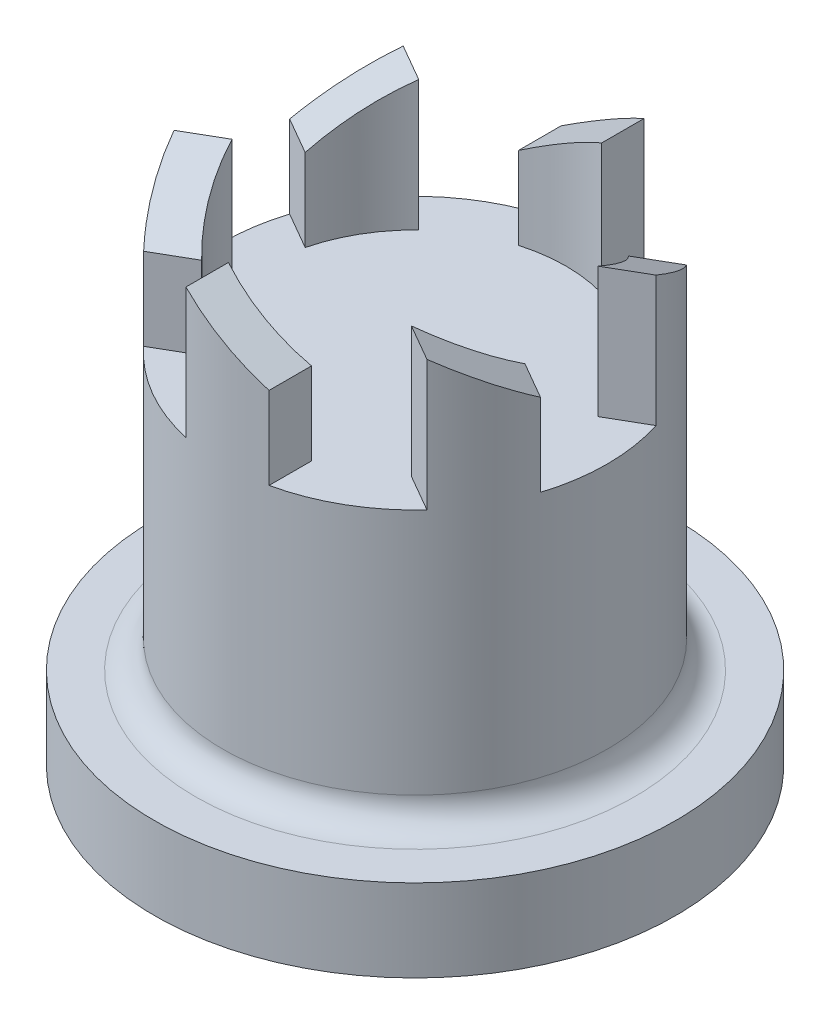
SolidWorks part; units mm, degrees
ref_plane "Front Plane" through (0, 0, 0) normal (0, 0, 1) x (1, 0, 0)
ref_plane "Top Plane" through (0, 0, 0) normal (0, 1, 0) x (1, 0, 0)
ref_plane "Right Plane" through (0, 0, 0) normal (1, 0, 0) x (0, 0, -1)
sketch "Sketch1" plane through (0, 0, 0) normal (0, 1, 0) x (1, 0, 0)
  circle A0 centre (0, 0) radius 7
  dimension "D1" = 14
extrude "Boss-Extrude1" add sketch "Sketch1" along normal blind 10
sketch "Sketch5" plane through (0, 10, 0) normal (0, 1, 0) x (1, 0, 0)
  line L2 (5.1616, 4.7285) -> (3.822, 3.9551)
  line L3 (-1.5142, 6.8343) -> (-1.5142, 5.2875)
  line L4 (-1.5142, 5.2875) -> (1.5142, 5.2875)
  line L5 (1.5142, 5.2875) -> (1.5142, 6.8343)
  line L6 (3.822, 3.9551) -> (5.3362, 1.3324)
  line L7 (5.3362, 1.3324) -> (6.6757, 2.1058)
  line L8 (6.6757, -2.1058) -> (5.3362, -1.3324)
  line L9 (5.3362, -1.3324) -> (3.822, -3.9551)
  line L10 (3.822, -3.9551) -> (5.1616, -4.7285)
  line L11 (1.5142, -6.8343) -> (1.5142, -5.2875)
  line L12 (1.5142, -5.2875) -> (-1.5142, -5.2875)
  line L13 (-1.5142, -5.2875) -> (-1.5142, -6.8343)
  line L14 (-5.1616, -4.7285) -> (-3.822, -3.9551)
  line L15 (-3.822, -3.9551) -> (-5.3362, -1.3324)
  line L16 (-5.3362, -1.3324) -> (-6.6757, -2.1058)
  line L17 (-6.6757, 2.1058) -> (-5.3362, 1.3324)
  line L18 (-5.3362, 1.3324) -> (-3.822, 3.9551)
  line L19 (-3.822, 3.9551) -> (-5.1616, 4.7285)
  arc A0 (-1.5142, 6.8343) -> (1.5142, 6.8343) centre (0, 0) cw
  circle A1 centre (0, 0) radius 7 construction
  circle A2 centre (0, 0) radius 5.5
  arc A3 (5.1616, 4.7285) -> (6.6757, 2.1058) centre (0, 0) cw
  arc A4 (6.6757, -2.1058) -> (5.1616, -4.7285) centre (0, 0) cw
  arc A5 (1.5142, -6.8343) -> (-1.5142, -6.8343) centre (0, 0) cw
  arc A6 (-5.1616, -4.7285) -> (-6.6757, -2.1058) centre (0, 0) cw
  arc A7 (-6.6757, 2.1058) -> (-5.1616, 4.7285) centre (0, 0) cw
  circle M7 centre (0, 0) radius 7
  dimension "D3" = 11
  dimension "D1" = 6
extrude "Boss-Extrude3" add sketch "Sketch5" along normal blind 5 contours A2 L19 L17 M7 | A2 L5 L3 M7 | A2 L7 L2 M7 | A2 L10 L8 M7 | A2 L13 L11 M7 | A2 L16 L14 M7 region at (5.358, 10, -3.0934) region at (0, 10, -6.1869) region at (5.358, 10, 3.0934) region at (-5.358, 10, -3.0934) region at (0, 10, 6.1869) region at (-5.358, 10, 3.0934)
chamfer "Chamfer2" distance 2 angle 60 6 edges at (1.5142, 15, 6.0609) (-4.4918, 15, 4.3418) (-6.006, 15, -1.7191) (-1.5142, 15, -6.0609) (4.4918, 15, -4.3418) (6.006, 15, 1.7191) first distance on face at (1.5142, 12.5, 6.0609) first distance on face at (-4.4918, 12.5, 4.3418) first distance on face at (-6.006, 12.5, -1.7191) first distance on face at (-1.5142, 12.5, -6.0609) first distance on face at (4.4918, 12.5, -4.3418) first distance on face at (6.006, 12.5, 1.7191)
sketch "Sketch7" plane through (0, 0, 0) normal (0, -1, 0) x (1, 0, 0)
  circle A2 centre (0, 0) radius 9.5
  circle A3 centre (0, 0) radius 9.5
  dimension "D1" = 2.5
extrude "Boss-Extrude4" add sketch "Sketch7" along normal blind 3
sketch "Sketch6" plane through (0, -3, 0) normal (0, -1, 0) x (1, 0, 0)
  line L0 (1.2247, 1.25) -> (-1.2247, 1.25)
  arc A1 (-1.2247, 1.25) -> (1.2247, 1.25) centre (0, 0) ccw
  dimension "D1" = 1.25
  dimension "D2" = 1.75
extrude "Cut-Extrude1" cut sketch "Sketch6" against normal blind 10
fillet "Fillet1" radius 1 1 edges at (0, 0, 7)
